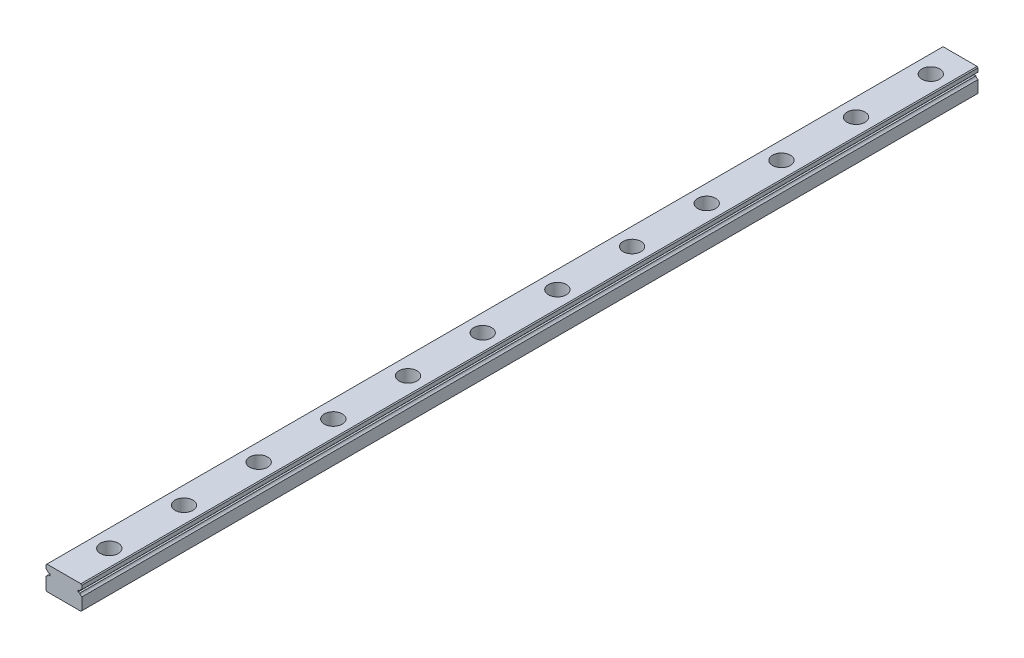
SolidWorks part; units mm, degrees
ref_plane "Спереди" through (0, 0, 0) normal (0, 0, 1) x (1, 0, 0)
ref_plane "Сверху" through (0, 0, 0) normal (0, 1, 0) x (1, 0, 0)
ref_plane "Справа" through (0, 0, 0) normal (1, 0, 0) x (0, 0, -1)
sketch "Эскиз1" plane through (0, 0, 0) normal (0, 0, 1) x (1, 0, 0)
  line L0 (-6, 3.7) -> (-5.7, 4)
  line L1 (-5.7, -4) -> (5.7, -4)
  line L2 (-6, -3.7) -> (-6, 0.3334)
  line L3 (-5.7, 4) -> (5.7, 4)
  line L4 (6, -3.7) -> (6, 0.3334)
  line L5 (-6, -4) -> (6, 4) construction
  line L6 (-6, 4) -> (6, -4) construction
  line L7 (-6, -3.7) -> (-5.7, -4)
  line L8 (5.7, -4) -> (6, -3.7)
  line L9 (5.7, 4) -> (6, 3.7)
  line L10 (-6, 2.4498) -> (-6, 3.7)
  line L11 (-5.2979, 1.7203) -> (-4.6875, 1.7203)
  line L12 (0, 5.4188) -> (0, -5.747) construction
  line L13 (-5.2922, 1.0823) -> (-4.6875, 1.0823)
  line L14 (-4.6875, 1.7203) -> (-4.6875, 1.0823)
  line L15 (4.6875, 1.7203) -> (4.6875, 1.0823)
  line L16 (5.2922, 1.0823) -> (4.6875, 1.0823)
  line L17 (5.2979, 1.7203) -> (4.6875, 1.7203)
  line L18 (6, 2.4498) -> (6, 3.7)
  arc A0 (-6, 0.3334) -> (-5.2922, 1.0823) centre (-6.3695, 1.3916) ccw
  arc A1 (-5.2979, 1.7203) -> (-6, 2.4498) centre (-6.3695, 1.3916) ccw
  arc A2 (5.2979, 1.7203) -> (6, 2.4498) centre (6.3695, 1.3916) cw
  arc A3 (6, 0.3334) -> (5.2922, 1.0823) centre (6.3695, 1.3916) cw
  point P0 (0, 0)
extrude "Бобышка-Вытянуть1" add sketch "Эскиз1" along normal blind 300
sketch "Эскиз2" plane through (0, 4, 0) normal (0, 1, 0) x (1, 0, 0)
  line L0 (0, 0) -> (0, -26.2396) construction
  line L1 (5.7, 0) -> (-5.7, 0) construction
  line L2 (-3.8306, -10) -> (4.207, -10) construction
  circle A0 centre (0.1882, -10) radius 3
  circle A1 centre (0.1882, -10) radius 1.75
  dimension "D1" = 10
extrude "Вырез-Вытянуть1" cut sketch "Эскиз2" against normal blind 4.5
extrude "Вырез-Вытянуть2" cut sketch "Эскиз2<2>" against normal through all contours A1 region at (0.1882, 4, 10)
sketch "Эскиз2<2>" plane through (0, 4, 0) normal (0, 1, 0) x (1, 0, 0) same geometry as "Эскиз2"
pattern_linear "Линейный массив1" count 12 spacing 25 along (0, 0, 1) of "Вырез-Вытянуть1", "Вырез-Вытянуть2"
